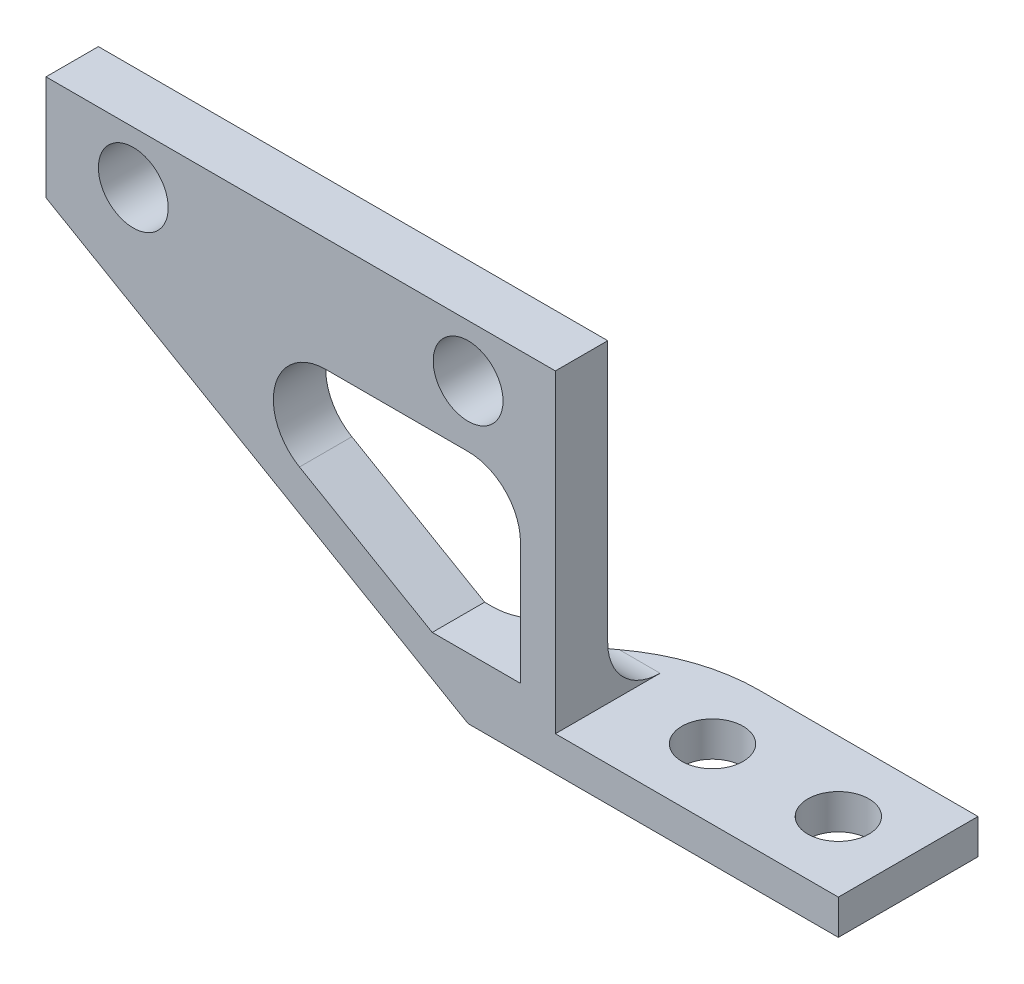
SolidWorks part; units mm, degrees
ref_plane "Front Plane" through (0, 0, 0) normal (0, 0, 1) x (1, 0, 0)
ref_plane "Top Plane" through (0, 0, 0) normal (0, 1, 0) x (1, 0, 0)
ref_plane "Right Plane" through (0, 0, 0) normal (1, 0, 0) x (0, 0, -1)
sketch "Sketch1" plane through (0, 0, 0) normal (0, 1, 0) x (1, 0, 0)
  line L0 (21.21, 4) -> (0, 4) construction
  line L1 (0, 0) -> (21.21, 0)
  line L2 (0, 0) -> (0, 8)
  line L3 (0, 8) -> (21.21, 8)
  line L4 (21.21, 0) -> (21.21, 8)
  line L5 (5, 8) -> (5, 0) construction
  circle A0 centre (10, 4) radius 1.75
  circle A1 centre (17.21, 4) radius 1.75
  dimension "D1" = 3.5
  dimension "D2" = 7.21
  dimension "D3" = 4
  dimension "D4" = 5
  dimension "D5" = 5
  dimension "D6" = 8
extrude "Boss-Extrude1" add sketch "Sketch1" along normal blind 2
sketch "Sketch2" plane through (0, 0, 0) normal (0, 0, 1) x (1, 0, 0)
  line L0 (5, 0) -> (5, 20)
  line L2 (5, 20) -> (-24.18, 20)
  line L3 (-24.18, 20) -> (-24.18, 14)
  line L7 (-24.18, 17) -> (5, 17) construction
  line L8 (0, 0) -> (-24.18, 14)
  line L9 (0, 0) -> (21.21, 0) construction
  line L10 (5, 0) -> (0, 0)
  line L11 (-2.0535, 3.5) -> (-19.3249, 13.5)
  line L12 (-19.3249, 13.5) -> (3, 13.5)
  line L13 (3, 13.5) -> (3, 3.5)
  line L14 (3, 3.5) -> (-2.0535, 3.5)
  line L15 (0, 2) -> (21.21, 2) construction
  circle A0 centre (-19.18, 17) radius 2
  circle A1 centre (0, 17) radius 2
  dimension "D2" = 4
  dimension "D5" = 19.18
  dimension "D1" = 5
  dimension "D3" = 6
  dimension "D4" = 5
  dimension "D6" = 5
  dimension "D7" = 20
  dimension "D8" = 2
  dimension "D9" = 2
  dimension "D10" = 1.5
  dimension "D11" = 3.5
extrude "Boss-Extrude2" add sketch "Sketch2" against normal blind 3
fillet "Fillet1" radius 10 1 edges at (0, 1, -8)
fillet "Fillet2" radius 3 4 edges at (2.5, 2, -3) (0, 1, -3) (3, 13.5, -1.5) (-19.3249, 13.5, -1.5)
